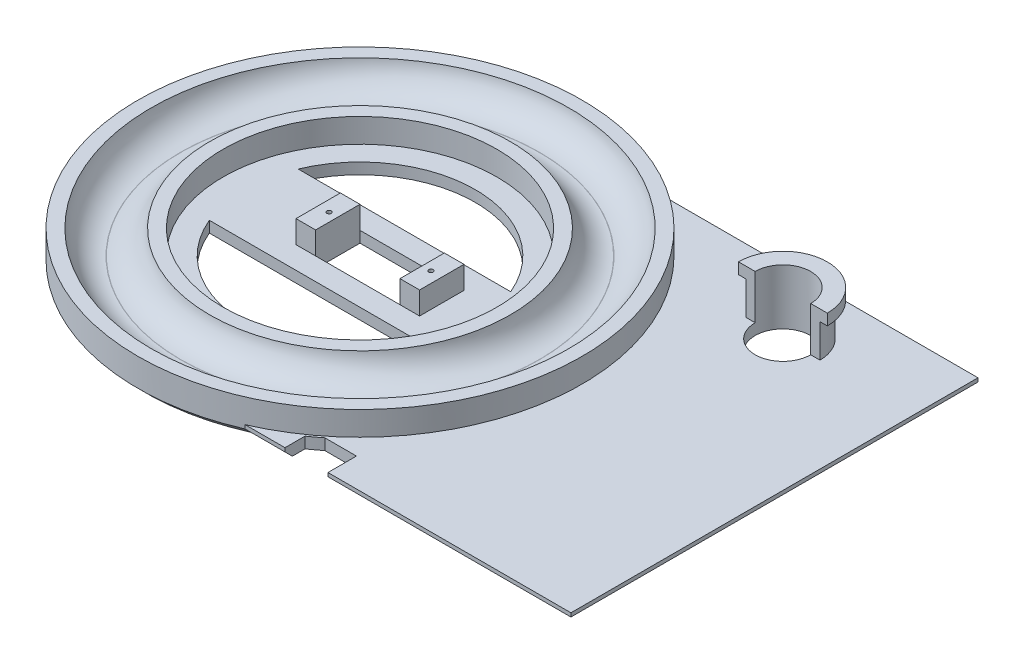
SolidWorks part; units mm, degrees
note: The reader was unsure of these and kept them because the rebuilt part matched: shared geometry of "Sketch7<3>".
ref_plane "Front Plane" through (0, 0, 0) normal (0, 0, 1) x (1, 0, 0)
ref_plane "Top Plane" through (0, 0, 0) normal (0, 1, 0) x (1, 0, 0)
ref_plane "Right Plane" through (0, 0, 0) normal (1, 0, 0) x (0, 0, -1)
sketch "Sketch1" plane through (0, 0, 0) normal (0, 1, 0) x (1, 0, 0)
  line L0 (0, 0) -> (0, 6) construction
  line L1 (0, 6) -> (-6, 6) construction
  line L2 (112, 55) -> (112, -55)
  line L3 (112, -55) -> (23.9792, -55)
  line L4 (23.9792, 55) -> (112, 55)
  line L5 (-6, 6) -> (-6, -6)
  line L6 (-6, -6) -> (16.8, -6)
  line L7 (16.8, -6) -> (16.8, 6)
  line L8 (16.8, 6) -> (-6, 6)
  circle A0 centre (0, 0) radius 48.3796 construction
  circle A1 centre (-43.9012, 20.3291) radius 7.5 construction
  circle A2 centre (-35.4705, 32.9003) radius 7.5 construction
  circle A3 centre (-23.5677, 42.251) radius 7.5 construction
  circle A4 centre (-9.3579, 47.4659) radius 7.5 construction
  circle A5 centre (5.7679, 48.0345) radius 7.5 construction
  circle A6 centre (20.3291, 43.9012) radius 7.5 construction
  circle A7 centre (32.9003, 35.4705) radius 7.5 construction
  circle A8 centre (42.251, 23.5677) radius 7.5 construction
  circle A9 centre (47.4659, 9.3579) radius 7.5 construction
  circle A10 centre (48.0345, -5.7679) radius 7.5 construction
  circle A11 centre (43.9012, -20.3291) radius 7.5 construction
  circle A12 centre (35.4705, -32.9003) radius 7.5 construction
  circle A13 centre (23.5677, -42.251) radius 7.5 construction
  circle A14 centre (9.3579, -47.4659) radius 7.5 construction
  circle A15 centre (-5.7679, -48.0345) radius 7.5 construction
  circle A16 centre (-20.3291, -43.9012) radius 7.5 construction
  circle A17 centre (-32.9003, -35.4705) radius 7.5 construction
  circle A18 centre (-42.251, -23.5677) radius 7.5 construction
  circle A19 centre (-47.4659, -9.3579) radius 7.5 construction
  circle A20 centre (-48.0345, 5.7679) radius 7.5 construction
  arc A21 (23.9792, 55) -> (23.9792, -55) centre (0, 0) ccw
  point P46 (0, 0)
  dimension "D1" = 20
  dimension "D2" = 60
  dimension "D6" = 96.7591
  dimension "D3" = 110
  dimension "D4" = 112
  dimension "D5" = 55
extrude "Boss-Extrude1" add sketch "Sketch1" along normal blind 3
sketch "Sketch2" plane through (0, 3, 0) normal (0, 1, 0) x (1, 0, 0)
  circle A0 centre (0, 0) radius 60
  circle A1 centre (0, 0) radius 48.38 construction
  circle A2 centre (0, 0) radius 56.4
  circle A3 centre (0, 48.38) radius 7.5 construction
  circle A4 centre (0, 0) radius 40.6
  circle A5 centre (0, 0) radius 37
  dimension "D1" = 3.6
  dimension "D4" = 112.8
  dimension "D5" = 81.2
  dimension "D6" = 74
extrude "Boss-Extrude2" add sketch "Sketch2" along normal blind 6.5
fillet "Fillet1" radius 8 2 edges at (0, 3, 40.6) (0, 3, 56.4)
sketch "Sketch3" plane through (0, 3, 0) normal (0, 1, 0) x (1, 0, 0)
  line L0 (-6, 0) -> (-8.35, 0) construction
  line L1 (-11.3, 6) -> (-6, 6)
  line L2 (-11.3, 6) -> (-11.3, -6)
  line L3 (-11.3, -6) -> (-6, -6)
  line L4 (-6, 6) -> (-6, -6)
  line L5 (16.8, 6) -> (22.1, 6)
  line L6 (16.8, 6) -> (16.8, -6)
  line L7 (16.8, -6) -> (22.1, -6)
  line L8 (22.1, 6) -> (22.1, -6)
  line L9 (16.8, 0) -> (19.156, 0) construction
  circle A0 centre (-8.35, 0) radius 0.6
  circle A1 centre (19.156, 0) radius 0.6
  dimension "D1" = 5.3
  dimension "D2" = 12
  dimension "D3" = 5.3
  dimension "D4" = 12
extrude "Boss-Extrude3" add sketch "Sketch3" along normal blind 6.1
chamfer "Chamfer1" distance 2 angle 45 4 edges at (67.9896, 0, -55) (112, 0, 0) (67.9896, 0, 55) (-60, 0, 0)
sketch "Sketch4" plane through (0, 0, 0) normal (0, -1, 0) x (1, 0, 0)
  line L1 (62.0174, 56.3006) -> (74.5794, 56.3006)
  line L2 (62.0174, 56.3006) -> (62.0174, 42.7752)
  line L3 (62.0174, 42.7752) -> (74.5794, 42.7752)
  line L4 (74.5794, 56.3006) -> (74.5794, 42.7752)
extrude "Cut-Extrude1" cut sketch "Sketch4" against normal blind 1
sketch "Sketch5" plane through (0, 0, 0) normal (0, -1, 0) x (1, 0, 0)
  circle A0 centre (0, 0) radius 39.5 construction
  circle A1 centre (-39.5, 0) radius 2
  circle A2 centre (19.75, 34.208) radius 2
  circle A3 centre (19.75, -34.208) radius 2
  point P11 (0, 0)
  dimension "D1" = 3
extrude "Cut-Extrude2" cut sketch "Sketch5" against normal blind 4
sketch "Sketch6" plane through (0, 3, 0) normal (0, 1, 0) x (1, 0, 0)
  line L0 (0, 0) -> (0, 12)
  line L1 (0, 12) -> (-28.7149, 12)
  line L2 (-28.7149, 12) -> (28.7149, 12)
  line L4 (28.7149, -12) -> (-28.7149, -12)
  arc A0 (-28.7149, -12) -> (28.7149, -12) centre (0, 0) ccw
  arc A1 (28.7149, 12) -> (-28.7149, 12) centre (0, 0) ccw
extrude "Cut-Extrude3" cut sketch "Sketch6" against normal blind 11.9 contours L2 A1 L1 | L4 A0
sketch "Sketch7" plane through (0, 3, 0) normal (0, 1, 0) x (1, 0, 0)
  line L0 (69.0118, 37.774) -> (66.5118, 37.774)
  line L1 (84.0118, 37.774) -> (86.5118, 37.774)
  circle A0 centre (76.5118, 37.774) radius 7.5
  arc A1 (86.5118, 37.774) -> (66.5118, 37.774) centre (76.5118, 37.774) ccw
  arc M3 (23.9792, 55) -> (23.9792, -55) centre (0, 0) cw
  dimension "D1" = 15
  dimension "D2" = 20
extrude "Cut-Extrude4" cut sketch "Sketch7" against normal blind 10 contours A0 M3
extrude "Boss-Extrude4" add sketch "Sketch7<3>" along normal blind 12 contours L1 A1 L0 A0
sketch "Sketch7<3>" plane through (0, 3, 0) normal (0, 1, 0) x (1, 0, 0) same geometry as "Sketch7"
sketch "Sketch8" plane through (0, 15, 0) normal (0, 1, 0) x (1, 0, 0)
  line L0 (76.5118, 37.774) -> (64.5118, 37.774)
  line L1 (76.5118, 37.774) -> (88.5118, 37.774)
  arc A0 (88.5118, 37.774) -> (64.5118, 37.774) centre (76.5118, 37.774) ccw
  arc A1 (84.0118, 37.774) -> (69.0118, 37.774) centre (76.5118, 37.774) ccw
  arc M3 (86.5118, 37.774) -> (66.5118, 37.774) centre (76.5118, 37.774) ccw
extrude "Boss-Extrude5" add sketch "Sketch8" against normal blind 3 contours L1 A0 L0 M3
sketch "Sketch9" plane through (0, 3, 0) normal (0, 1, 0) x (1, 0, 0)
  line L0 (34.7199, -55) -> (46.3404, -55)
  line L1 (23.9792, -55) -> (112, -55) construction
  line L2 (46.3404, -55) -> (46.3404, -47.3)
  line L3 (46.3404, -47.3) -> (37.7739, -47.3)
  line L4 (34.7199, -49.5852) -> (34.7199, -55)
  arc A0 (34.7199, -49.5852) -> (37.7739, -47.3) centre (0, 0) ccw
extrude "Cut-Extrude5" cut sketch "Sketch9" against normal blind 12
